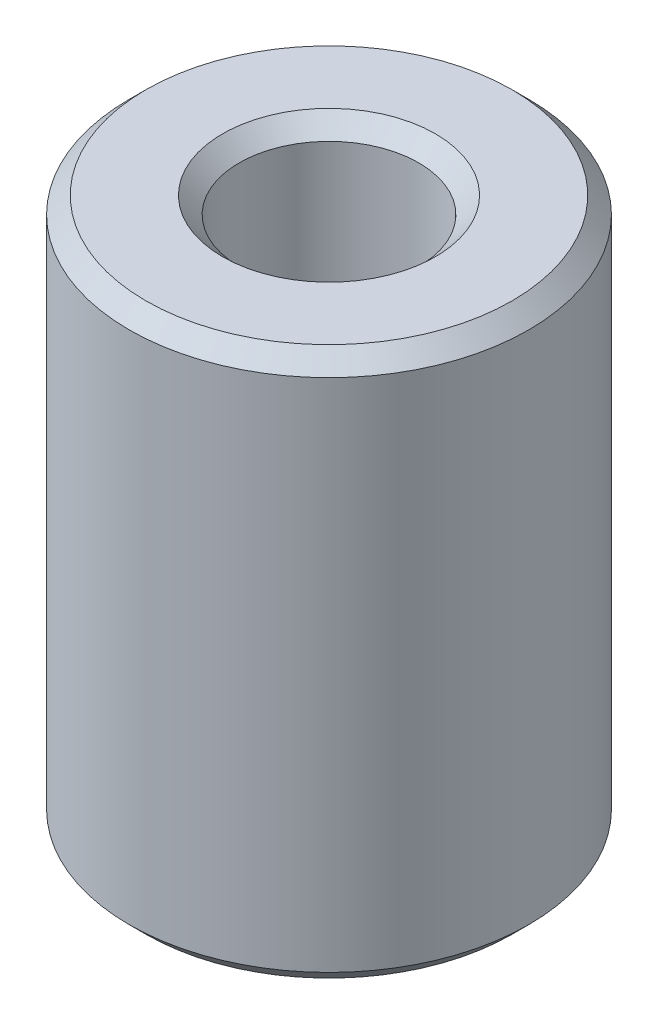
SolidWorks part; units mm, degrees
ref_plane "Front Plane" through (0, 0, 0) normal (0, 0, 1) x (1, 0, 0)
ref_plane "Top Plane" through (0, 0, 0) normal (0, 1, 0) x (1, 0, 0)
ref_plane "Right Plane" through (0, 0, 0) normal (1, 0, 0) x (0, 0, -1)
sketch "Sketch1" plane through (0, 0, 0) normal (0, 1, 0) x (1, 0, 0)
  circle A0 centre (0, 0) radius 15
  dimension "SLEEVE_OD" = 30
extrude "Boss-Extrude1" add sketch "Sketch1" along normal blind 41.2007
sketch "Sketch2" plane through (0, 0, 0) normal (0, 1, 0) x (1, 0, 0)
  circle A0 centre (0, 0) radius 6.7407
  dimension "BORE_D" = 13.4813
extrude "Cut-Extrude1" cut sketch "Sketch2" along normal through all
chamfer "Chamfer1" distance 1.2568 angle 45 4 edges at (0, 41.2007, 6.7407) (0, 0, 6.7407) (0, 0, 15) (0, 41.2007, 15)
